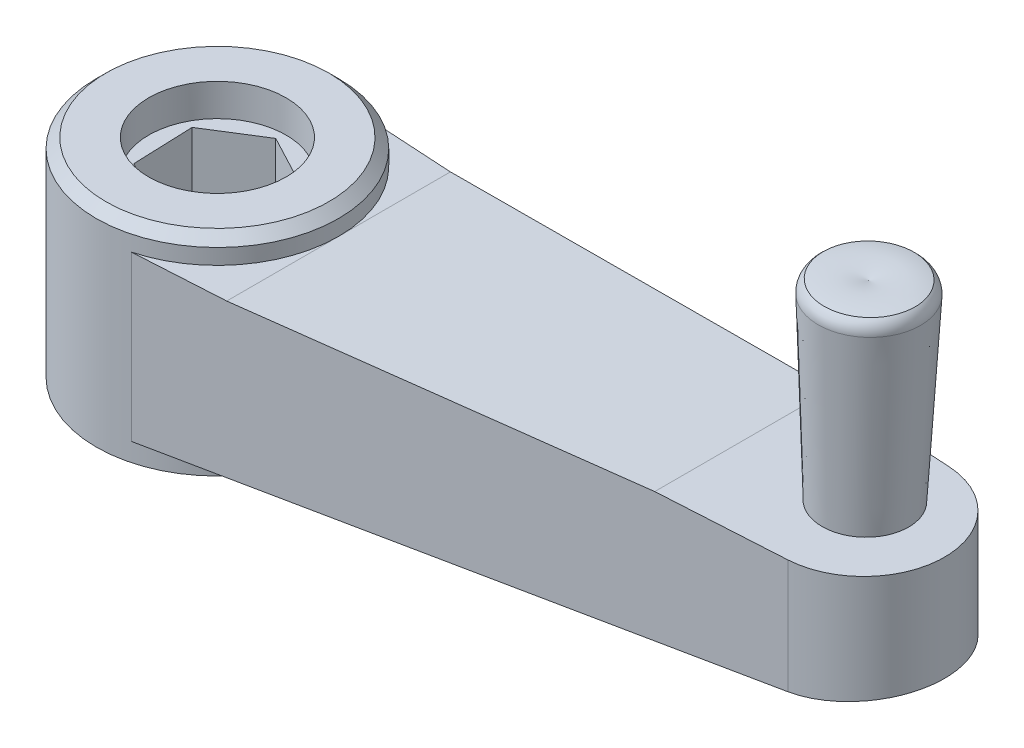
SolidWorks part; units mm, degrees
ref_plane "Plan de face" through (0, 0, 0) normal (0, 0, 1) x (1, 0, 0)
ref_plane "Plan de dessus" through (0, 0, 0) normal (0, 1, 0) x (1, 0, 0)
ref_plane "Plan de droite" through (0, 0, 0) normal (1, 0, 0) x (0, 0, -1)
ref_plane "Plan4" through (0, 26, 0) normal (0, 1, 0) x (-1, 0, 0)
sketch "Esquisse1" plane through (0, 26, 0) normal (0, 1, 0) x (-1, 0, 0)
  line L0 (-0.8636, 14.6746) -> (-80.5875, 9.9827)
  line L1 (-80.5875, -9.9827) -> (-0.8636, -14.6746)
  arc A0 (-0.8636, -14.6746) -> (-0.8636, 14.6746) centre (0, 0) ccw
  arc A1 (-80.5875, 9.9827) -> (-80.5875, -9.9827) centre (-80, 0) ccw
extrude "Boss.-Extru.1" add sketch "Esquisse1" against normal blind 25.7
sketch "Esquisse2" plane through (0, 0, 0) normal (0, 0, 1) x (1, 0, 0)
  line L0 (-21, 22.88) -> (15, 22.88)
  line L1 (15, 22.88) -> (70, 26.31)
  line L2 (70, 26.31) -> (90, 26.31)
  line L3 (90, 26.31) -> (90, 72.8393)
  line L4 (90, 72.8393) -> (-21, 72.8393)
  line L5 (-21, 72.8393) -> (-21, 22.88)
extrude "Enlèv. mat.-Extru.1" cut sketch "Esquisse2" along normal blind 80 and the other way blind 80
sketch "Esquisse3" plane through (0, 0, 0) normal (0, 0, 1) x (1, 0, 0)
  line L0 (-25, -30.1858) -> (90.01, -30.1858)
  line L1 (90.01, -30.1858) -> (90.01, 13)
  line L2 (90.01, 13) -> (-25, -0.8985)
  line L3 (-25, -0.8985) -> (-25, -30.1858)
sketch "Esquisse4" plane through (0, 0, 0) normal (0, 0, 1) x (1, 0, 0)
  line L0 (0, 26) -> (13.8, 26)
  line L1 (13.8, 26) -> (15, 24.8)
  line L2 (15, 24.8) -> (15, 0.3)
  line L3 (15, 0.3) -> (11, 0.3)
  line L4 (11, 0.3) -> (11, 0)
  line L5 (11, 0) -> (0, 0)
  line L6 (0, 0) -> (0, 26)
  line L7 (0, 0) -> (0, 26) construction
extrude "Enlèv. mat.-Extru.2" cut sketch "Esquisse3" along normal blind 80 and the other way blind 80
revolve "Révolution1" add sketch "Esquisse4" angle 360 about L7 reverse direction yes
sketch "Esquisse5" plane through (0, 0, 0) normal (0, 0, 1) x (1, 0, 0)
  line L0 (0, 52) -> (8.5, 52)
  line L1 (8.5, 52) -> (8.5, 22)
  line L2 (8.5, 22) -> (0, 22)
  line L3 (0, 22) -> (0, 52)
  line L4 (0, 22) -> (0, 52) construction
revolve "Enlèvement de matière-Révolution1" cut sketch "Esquisse5" angle 360 about L4 reverse direction yes
ref_plane "Plan5" through (0, 22, 0) normal (0, 1, 0) x (-1, 0, 0)
sketch "Esquisse6" plane through (0, 22, 0) normal (0, 1, 0) x (-1, 0, 0)
  line L2 (0, -7.0992) -> (0, -7.0711)
sketch "Esquisse7" plane through (0, 0, 0) normal (0, 0, 1) x (1, 0, 0)
  line L0 (86.3492, 51) -> (87.1429, 51)
  line L1 (87.1429, 51) -> (85.5556, 27)
  line L2 (85.5556, 27) -> (83, 27)
  line L3 (83, 27) -> (83, 21.1135)
  line L4 (83, 21.1135) -> (82.3865, 20.5)
  line L5 (82.3865, 20.5) -> (80, 20.5)
  line L6 (80, 20.5) -> (80.6626, 51)
  line L7 (80, 20.5) -> (80.6626, 51) construction
  arc A0 (80.6626, 51) -> (86.3492, 51) centre (83.5059, 38.4205) cw
revolve "Révolution2" add sketch "Esquisse7" angle 360 about L7 reverse direction yes
ref_plane "Plan6" through (0, 1, 0) normal (0, 1, 0) x (-1, 0, 0)
fillet "Congé4" radius 2 1 edges at (74.1885, 51.2814, 0)
sketch "Esquisse8" plane through (0, 22, 0) normal (0, 1, 0) x (-1, 0, 0)
  line L1 (-0.2783, 7.5004) -> (-6.6347, 3.5091)
  line L2 (-6.6347, 3.5091) -> (-6.3564, -3.9912)
  line L3 (-6.3564, -3.9912) -> (0.2783, -7.5004)
  line L4 (0.2783, -7.5004) -> (6.6347, -3.5091)
  line L5 (6.6347, -3.5091) -> (6.3564, 3.9912)
  line L6 (6.3564, 3.9912) -> (-0.2783, 7.5004)
  circle A0 centre (0, 0) radius 6.5 construction
  dimension "D1" = 13
extrude "Enlèv. mat.-Extru.3" cut sketch "Esquisse8" against normal through all
